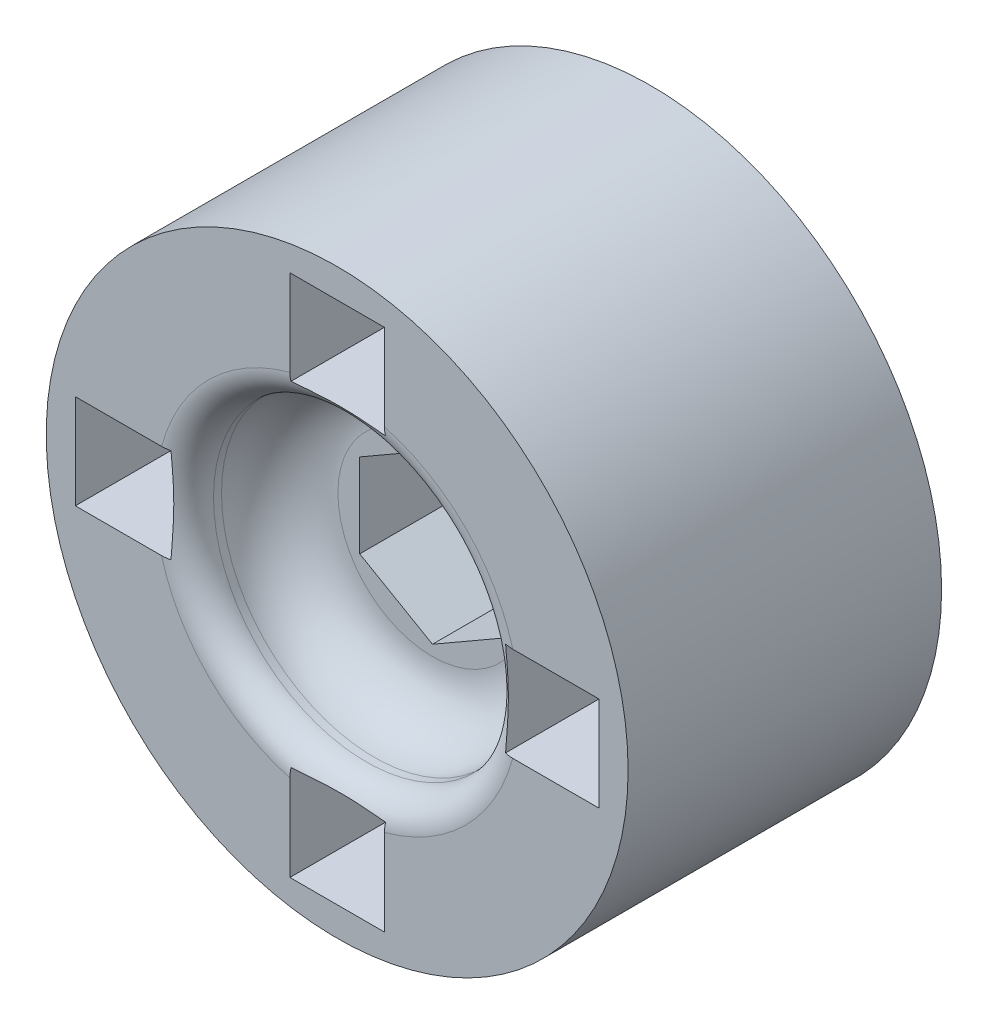
SolidWorks part; units mm, degrees
ref_plane "Front Plane" through (0, 0, 0) normal (0, 0, 1) x (1, 0, 0)
ref_plane "Top Plane" through (0, 0, 0) normal (0, 1, 0) x (1, 0, 0)
ref_plane "Right Plane" through (0, 0, 0) normal (1, 0, 0) x (0, 0, -1)
sketch "Sketch1" plane through (0, 0, 0) normal (0, 0, 1) x (1, 0, 0)
  circle A0 centre (-11.8226, 14.5298) radius 20
  circle A1 centre (-11.8226, 14.5298) radius 1
  dimension "D1" = 40
  dimension "D2" = 2
extrude "Boss-Extrude1" add sketch "Sketch1" along normal blind 21.55
hole_wizard "Tap Drill for M5x0.8 Tap1" positions "Sketch2" profile "Sketch3" hole size "M5x0.8" standard "ANSI Metric"
sketch "Sketch2" plane through (0, 0, 21.55) normal (0, 0, 1) x (1, 0, 0)
  point P0 (-11.8226, 14.5298)
sketch "Sketch3" plane through (-11.8226, 14.5298, 21.55) normal (1, 0, 0) x (0, -1, 0)
  line L0 (0, 0) -> (0, 6.2618)
  line L1 (0, 6.2618) -> (2.1, 5)
  line L2 (2.1, 5) -> (2.1, 0)
  line L5 (2.1, 0) -> (0, 0)
  line L10 (0, 6.2618) -> (-2.1, 5) construction
  line L11 (0, -6.35) -> (0, 107.95) construction
  dimension "Hole Dia." = 4.2
  dimension "Hole Depth" = 5
  dimension "Drill Angle" = 118
sketch "Sketch4" plane through (0, 0, 21.55) normal (0, 0, 1) x (1, 0, 0)
  line L1 (6.1774, 17.7798) -> (-0.3226, 17.7798)
  line L2 (6.1774, 17.7798) -> (6.1774, 11.2798)
  line L3 (6.1774, 11.2798) -> (-0.3226, 11.2798)
  line L4 (-0.3226, 17.7798) -> (-0.3226, 11.2798)
  circle A0 centre (-11.8226, 14.5298) radius 1 construction
  circle A1 centre (-11.8226, 14.5298) radius 20 construction
  dimension "D1" = 6.5
  dimension "D2" = 6.5
  dimension "D3" = 3.25
  dimension "D4" = 18
extrude "Cut-Extrude1" cut sketch "Sketch4" against normal offset from surface (19.05 mm away) 2.5 up to face at (8.1774, 14.5298, 0)
ref_axis "Axis1" through (-11.8226, 14.5298, 21.55) along (0, 0, -1)
pattern_circular "CirPattern1" count 4 over 360 about axis through (-11.8226, 14.5298, 21.55) along (0, 0, -1) of "Cut-Extrude1"
sketch "Sketch5" plane through (0, 0, 0) normal (0, 0, -1) x (-1, 0, 0)
  circle A0 centre (11.8226, 14.5298) radius 5
  circle A1 centre (11.8226, 14.5298) radius 6
  circle M2 centre (11.8226, 14.5298) radius 1
  dimension "D1" = 10
  dimension "D2" = 12
extrude "Cut-Extrude2" cut sketch "Sketch5" against normal blind 1 contours A1 A0 | A0 M2 region at (-6.964, 14.5298, 0) region at (-5.9923, 14.5298, 0)
sketch "Sketch6" plane through (0, 0, 21.55) normal (0, 0, 1) x (1, 0, 0)
  line L0 (-16.8226, 17.416) -> (-11.8226, 20.2957)
  line L1 (-6.8226, 11.6435) -> (-16.8226, 11.6435)
  line L2 (-6.8226, 11.6435) -> (-6.8226, 17.416)
  line L3 (-6.8226, 17.416) -> (-16.8226, 17.416)
  line L4 (-16.8226, 11.6435) -> (-16.8226, 17.416)
  line L5 (-6.8226, 11.6435) -> (-16.8226, 17.416) construction
  line L6 (-6.8226, 17.416) -> (-16.8226, 11.6435) construction
  line L7 (-11.8226, 20.2957) -> (-6.8226, 17.416)
  line L8 (-6.8226, 11.6435) -> (-11.8226, 8.7638)
  line L9 (-11.8226, 8.7638) -> (-16.8226, 11.6435)
  point P0 (-11.8226, 14.5298)
  circle M25 centre (-11.8226, 14.5298) radius 2.1
  dimension "D1" = 10
  dimension "D2" = 5.7725
  dimension "D3" = 5.77
  dimension "D4" = 5.77
  dimension "D5" = 5.77
  dimension "D6" = 5.77
extrude "Cut-Extrude3" cut sketch "Sketch6" against normal up to surface (21.55 mm away) contours L4 L1 L2 L3 M25 | M25 | L7 L0 L3 | L9 L8 L1 region at (-11.8226, 18.3759, 21.55) region at (-11.8226, 17.3005, 21.55) region at (-11.8226, 10.6836, 21.55) region at (-11.8226, 14.5298, 21.55) up to face at (-17.8226, 14.5298, 0)
sketch "Sketch7" plane through (0, 0, 21.55) normal (0, 0, 1) x (1, 0, 0)
  circle A0 centre (-11.8226, 14.5298) radius 10.5
  dimension "D1" = 21
extrude "Cut-Extrude4" cut sketch "Sketch7" against normal offset from surface (6.55 mm away) 15 up to face at (-17.8226, 14.5298, 0)
fillet "Fillet4" radius 2 1 edges at (-1.3226, 14.5298, 21.55)
fillet "Fillet5" radius 4 1 edges at (-1.3226, 14.5298, 15)
equation "\"D2@Sketch4\"=6.5"
equation "\"D3@Sketch4\"=6.5/2"
equation "\"oringdiameter\"= 11"
equation "\"oringthickness\"= 2"
equation "\"D2@Sketch5\"=\"oringdiameter\" + \"oringthickness\"/2"
equation "\"D1@Sketch5\"=\"oringdiameter\" - \"oringthickness\"/2"
equation "\"D1@Cut-Extrude2\"= \"oringthickness\"/2"
equation "\"D1@Boss-Extrude1\"= 2.5 + (25.4*3/4)"
equation "\"D2@Sketch6\"=4.618*10/8"
